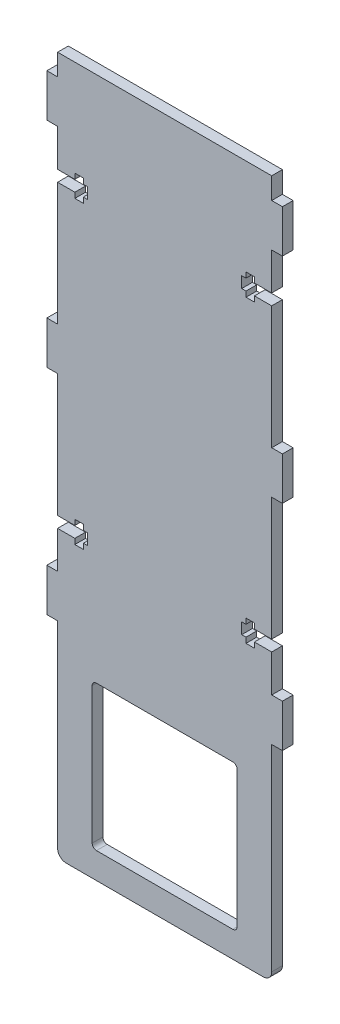
SolidWorks part; units mm, degrees
ref_plane "Front Plane" through (0, 0, 0) normal (0, 0, 1) x (1, 0, 0)
ref_plane "Top Plane" through (0, 0, 0) normal (0, 1, 0) x (1, 0, 0)
ref_plane "Right Plane" through (0, 0, 0) normal (1, 0, 0) x (0, 0, -1)
sketch "Sketch1" plane through (0, 0, 0) normal (0, 0, 1) x (1, 0, 0)
  line L1 (0, 0) -> (63.5, 0)
  line L2 (0, 0) -> (0, 152.4)
  line L3 (0, 152.4) -> (63.5, 152.4)
  line L4 (63.5, 0) -> (63.5, 152.4)
  dimension "D1" = 152.4
  dimension "D2" = 63.5
extrude "Boss-Extrude1" add sketch "Sketch1" along normal blind 3.175
sketch "Sketch2" plane through (0, 0, 3.175) normal (0, 0, 1) x (1, 0, 0)
  line L0 (0, 76.2) -> (63.5, 76.2) construction
  line L1 (0, 146.05) -> (-3.175, 146.05)
  line L2 (0, 146.05) -> (0, 133.35)
  line L3 (0, 133.35) -> (-3.175, 133.35)
  line L4 (-3.175, 146.05) -> (-3.175, 133.35)
  line L5 (0, 6.35) -> (-3.175, 6.35)
  line L6 (0, 6.35) -> (0, 19.05)
  line L7 (0, 19.05) -> (-3.175, 19.05)
  line L8 (-3.175, 6.35) -> (-3.175, 19.05)
  line L9 (0, 152.4) -> (0, 0) construction
  line L10 (63.5, 0) -> (63.5, 152.4) construction
  line L11 (-3.175, 76.2) -> (0, 76.2) construction
  line L12 (0, 82.55) -> (-3.175, 82.55)
  line L13 (0, 82.55) -> (0, 69.85)
  line L14 (0, 69.85) -> (-3.175, 69.85)
  line L15 (-3.175, 82.55) -> (-3.175, 69.85)
  line L16 (31.75, 152.4) -> (31.75, 0) construction
  line L17 (63.5, 152.4) -> (0, 152.4) construction
  line L18 (0, 0) -> (63.5, 0) construction
  line L19 (66.675, 146.05) -> (66.675, 133.35)
  line L20 (63.5, 133.35) -> (66.675, 133.35)
  line L21 (63.5, 146.05) -> (63.5, 133.35)
  line L22 (63.5, 146.05) -> (66.675, 146.05)
  line L23 (0, 82.55) -> (-3.175, 82.55)
  line L24 (0, 69.85) -> (-3.175, 69.85)
  line L25 (0, 82.55) -> (-3.175, 82.55)
  line L26 (0, 69.85) -> (-3.175, 69.85)
  line L27 (0, 82.55) -> (-3.175, 82.55)
  line L28 (0, 69.85) -> (-3.175, 69.85)
  line L29 (66.675, 6.35) -> (66.675, 19.05)
  line L30 (63.5, 19.05) -> (66.675, 19.05)
  line L31 (63.5, 6.35) -> (63.5, 19.05)
  line L32 (63.5, 6.35) -> (66.675, 6.35)
  line L33 (0, 82.55) -> (-3.175, 82.55)
  line L34 (0, 69.85) -> (-3.175, 69.85)
  line L35 (0, 82.55) -> (-3.175, 82.55)
  line L36 (0, 69.85) -> (-3.175, 69.85)
  line L37 (0, 82.55) -> (-3.175, 82.55)
  line L38 (0, 69.85) -> (-3.175, 69.85)
  line L39 (0, 82.55) -> (-3.175, 82.55)
  line L40 (0, 69.85) -> (-3.175, 69.85)
  line L41 (66.675, 76.2) -> (63.5, 76.2) construction
  line L42 (63.5, 69.85) -> (66.675, 69.85)
  line L43 (63.5, 82.55) -> (66.675, 82.55)
  line L44 (63.5, 69.85) -> (66.675, 69.85)
  line L45 (63.5, 82.55) -> (66.675, 82.55)
  line L46 (63.5, 69.85) -> (66.675, 69.85)
  line L47 (63.5, 82.55) -> (66.675, 82.55)
  line L48 (63.5, 69.85) -> (66.675, 69.85)
  line L49 (63.5, 82.55) -> (66.675, 82.55)
  line L50 (63.5, 69.85) -> (66.675, 69.85)
  line L51 (63.5, 82.55) -> (66.675, 82.55)
  line L52 (63.5, 69.85) -> (66.675, 69.85)
  line L53 (63.5, 82.55) -> (66.675, 82.55)
  line L54 (63.5, 69.85) -> (66.675, 69.85)
  line L55 (63.5, 82.55) -> (66.675, 82.55)
  line L56 (66.675, 82.55) -> (66.675, 69.85)
  line L57 (63.5, 69.85) -> (66.675, 69.85)
  line L58 (63.5, 82.55) -> (63.5, 69.85)
  line L59 (63.5, 82.55) -> (66.675, 82.55)
  line M1 (0, 152.4) -> (0, 0)
  line M3 (63.5, 0) -> (63.5, 152.4)
  dimension "D1" = 3.175
  dimension "D2" = 12.7
  dimension "D3" = 12.7
  dimension "D4" = 12.7
  dimension "D5" = 3.175
  dimension "D6" = 6.35
  dimension "D7" = 6.35
extrude "Boss-Extrude3" add sketch "Sketch2" against normal blind 3.175 contours L12 L15 L14 M1 | L22 L20 L19 M3 | L56 L43 L42 M3 | L32 L29 L30 M3 | L8 L5 L7 M1 | L4 L3 L2 L1 region at (-1.5875, 12.7, 3.175) region at (-1.5875, 76.2, 3.175) region at (65.0875, 12.7, 3.175) region at (65.0875, 76.2, 3.175) region at (65.0875, 139.7, 3.175)
sketch "Sketch4" plane through (0, 0, 3.175) normal (0, 0, 1) x (1, 0, 0)
  line L0 (31.75, 152.4) -> (31.75, 0) construction
  line L1 (63.5, 152.4) -> (0, 152.4) construction
  line L2 (0, 0) -> (63.5, 0) construction
  line L3 (0, 133.35) -> (0, 82.55) construction
  line L4 (0, 122.301) -> (8.89, 122.301)
  line L5 (0, 122.301) -> (0, 118.999)
  line L6 (0, 118.999) -> (8.89, 118.999)
  line L7 (8.89, 122.301) -> (8.89, 118.999)
  line L8 (5.12, 120.65) -> (7.62, 120.65) construction
  line L9 (5.12, 123.9) -> (7.62, 123.9)
  line L10 (5.12, 123.9) -> (5.12, 117.4)
  line L11 (5.12, 117.4) -> (7.62, 117.4)
  line L12 (7.62, 123.9) -> (7.62, 117.4)
  line L13 (0, 120.65) -> (8.89, 120.65) construction
  line L14 (0, 133.35) -> (-3.175, 133.35) construction
  line L15 (-3.175, 76.2) -> (66.675, 76.2) construction
  line L16 (-3.175, 82.55) -> (-3.175, 69.85) construction
  line L17 (66.675, 82.55) -> (66.675, 69.85) construction
  line L18 (0, 31.75) -> (8.89, 31.75) construction
  line L19 (5.12, 31.75) -> (7.62, 31.75) construction
  line L20 (7.62, 28.5) -> (7.62, 35)
  line L21 (5.12, 35) -> (7.62, 35)
  line L22 (5.12, 28.5) -> (5.12, 35)
  line L23 (5.12, 28.5) -> (7.62, 28.5)
  line L24 (8.89, 30.099) -> (8.89, 33.401)
  line L25 (0, 33.401) -> (8.89, 33.401)
  line L26 (0, 30.099) -> (0, 33.401)
  line L27 (0, 30.099) -> (8.89, 30.099)
  line L28 (58.38, 31.75) -> (55.88, 31.75) construction
  line L29 (63.5, 31.75) -> (54.61, 31.75) construction
  line L30 (63.5, 120.65) -> (54.61, 120.65) construction
  line L31 (58.38, 120.65) -> (55.88, 120.65) construction
  line L32 (63.5, 30.099) -> (54.61, 30.099)
  line L33 (63.5, 30.099) -> (63.5, 33.401)
  line L34 (63.5, 33.401) -> (54.61, 33.401)
  line L35 (54.61, 30.099) -> (54.61, 33.401)
  line L36 (58.38, 28.5) -> (55.88, 28.5)
  line L37 (58.38, 28.5) -> (58.38, 35)
  line L38 (58.38, 35) -> (55.88, 35)
  line L39 (55.88, 28.5) -> (55.88, 35)
  line L40 (55.88, 123.9) -> (55.88, 117.4)
  line L41 (58.38, 117.4) -> (55.88, 117.4)
  line L42 (58.38, 123.9) -> (58.38, 117.4)
  line L43 (58.38, 123.9) -> (55.88, 123.9)
  line L44 (54.61, 122.301) -> (54.61, 118.999)
  line L45 (63.5, 118.999) -> (54.61, 118.999)
  line L46 (63.5, 122.301) -> (63.5, 118.999)
  line L47 (63.5, 122.301) -> (54.61, 122.301)
  dimension "D1" = 3.302
  dimension "D2" = 6.5
  dimension "D3" = 2.5
  dimension "D4" = 1.27
  dimension "D5" = 8.89
  dimension "D6" = 12.7
extrude "Cut-Extrude4" cut sketch "Sketch4" against normal blind 3.175 contours L6 L7 L4 L5 | L9 L12 L11 L10 | L21 L20 L23 L22 | L24 L25 L26 L27 | L35 L34 L33 L32 | L38 L39 L36 L37 | L41 L40 L43 L42 | L45 L44 L47 L46
sketch "Sketch5" plane through (0, 0, 3.175) normal (0, 0, 1) x (1, 0, 0)
  line L0 (0, 0) -> (63.5, 0) construction
  line L1 (0, 0) -> (63.5, 0)
  line L2 (0, 0) -> (0, -50.8)
  line L3 (0, -50.8) -> (63.5, -50.8)
  line L4 (63.5, 0) -> (63.5, -50.8)
  line L5 (31.75, 0) -> (31.75, -50.8) construction
  line L6 (0, -25.4) -> (63.5, -25.4) construction
  line L8 (10.25, -3.9) -> (53.25, -3.9)
  line L9 (10.25, -3.9) -> (10.25, -46.9)
  line L10 (10.25, -46.9) -> (53.25, -46.9)
  line L11 (53.25, -3.9) -> (53.25, -46.9)
  line L12 (10.25, -3.9) -> (53.25, -46.9) construction
  line L13 (10.25, -46.9) -> (53.25, -3.9) construction
  point P12 (31.75, -25.4)
  dimension "D1" = 50.8
  dimension "D2" = 43
  dimension "D3" = 43
extrude "Boss-Extrude4" add sketch "Sketch5" against normal blind 3.175
sketch "Sketch7" plane through (0, 0, 3.175) normal (0, 0, 1) x (1, 0, 0)
  line L0 (63.5, -50.8) -> (63.5, 6.35) construction
  line L1 (0, -50.8) -> (63.5, -50.8)
  line L2 (0, -50.8) -> (0, -54.61)
  line L3 (0, -54.61) -> (63.5, -54.61)
  line L4 (63.5, -50.8) -> (63.5, -54.61)
  dimension "D1" = 3.81
extrude "Boss-Extrude5" add sketch "Sketch7" against normal blind 3.175
fillet "Fillet1" radius 2.54 2 edges at (63.5, -54.61, 1.5875) (0, -54.61, 1.5875)
fillet "Fillet2" radius 1.27 4 edges at (53.25, -46.9, 1.5875) (53.25, -3.9, 1.5875) (10.25, -3.9, 1.5875) (10.25, -46.9, 1.5875)
